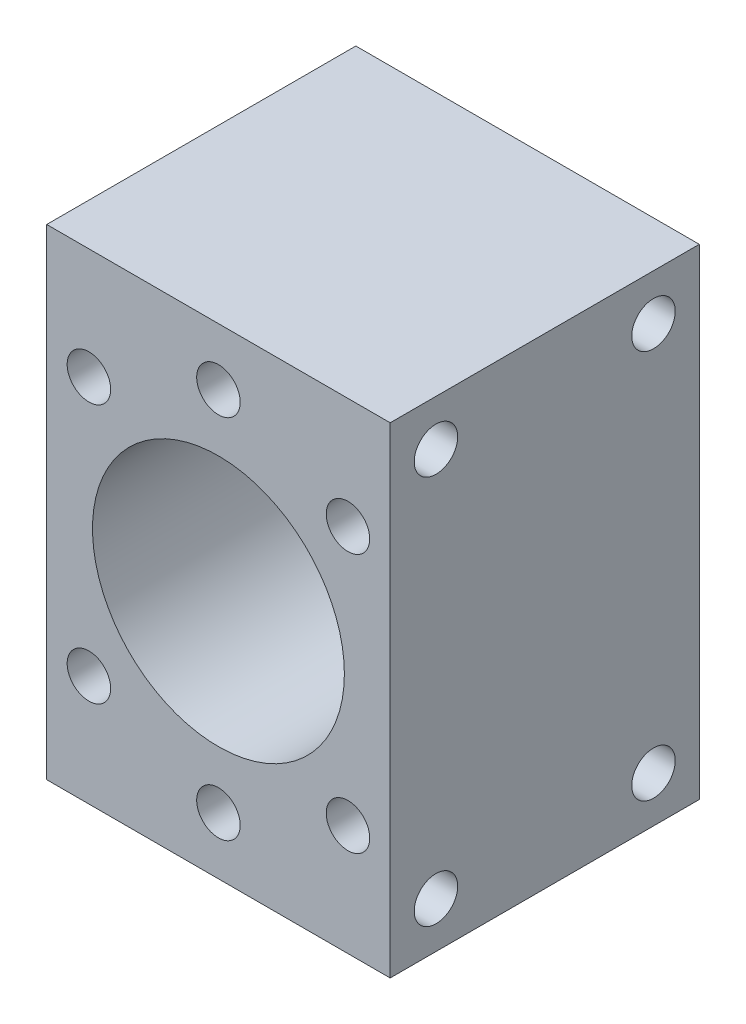
SolidWorks part; units mm, degrees
ref_plane "Front Plane" through (0, 0, 0) normal (0, 0, 1) x (1, 0, 0)
ref_plane "Top Plane" through (0, 0, 0) normal (0, 1, 0) x (1, 0, 0)
ref_plane "Right Plane" through (0, 0, 0) normal (1, 0, 0) x (0, 0, -1)
sketch "Sketch1" plane through (0, 0, 0) normal (0, 0, 1) x (1, 0, 0)
  line L3 (-15, -21) -> (15, -21)
  line L4 (-15, -21) -> (-15, 21)
  line L5 (-15, 21) -> (15, 21)
  line L6 (15, -21) -> (15, 21)
  line L7 (-15, -21) -> (15, 21) construction
  line L8 (-15, 21) -> (15, -21) construction
  dimension "D4" = 30
  dimension "D5" = 42
extrude "Boss-Extrude1" add sketch "Sketch1" along normal mid plane 27
sketch "Sketch2" plane through (0, 0, 13.5) normal (0, 0, 1) x (1, 0, 0)
  circle A0 centre (0, 0) radius 11
  dimension "D1" = 22
extrude "Cut-Extrude1" cut sketch "Sketch2" against normal through all
sketch "Sketch3" plane through (0, 0, 13.5) normal (0, 0, 1) x (1, 0, 0)
  line L0 (0, 21) -> (0, -21) construction
  line L1 (0, 0) -> (-19.8057, 19.8057) construction
  line L2 (0, 0) -> (19.0248, 19.0248) construction
  circle A2 centre (0, 0) radius 16 construction
  circle A3 centre (-11.3137, 11.3137) radius 1.9
  circle A4 centre (0, 16) radius 1.9
  circle A5 centre (11.3137, 11.3137) radius 1.9
  circle A6 centre (11.3137, -11.3137) radius 1.9
  circle A7 centre (0, -16) radius 1.9
  circle A8 centre (-11.3137, -11.3137) radius 1.9
  dimension "D3" = 32
  dimension "D4" = 3.8
  dimension "D5" = 3.8
  dimension "D6" = 3.8
  dimension "D7" = 3.8
  dimension "D8" = 3.8
  dimension "D9" = 3.8
  dimension "D1" = 45
  dimension "D2" = 45
extrude "Cut-Extrude2" cut sketch "Sketch3" against normal blind 10
sketch "Sketch6" plane through (15, 0, 0) normal (1, 0, 0) x (0, 0, -1)
  line L1 (-9.5, -17) -> (9.5, -17) construction
  line L2 (-9.5, -17) -> (-9.5, 17) construction
  line L3 (-9.5, 17) -> (9.5, 17) construction
  line L4 (9.5, -17) -> (9.5, 17) construction
  line L5 (-9.5, -17) -> (9.5, 17) construction
  line L6 (-9.5, 17) -> (9.5, -17) construction
  circle A0 centre (9.5, 17) radius 1.9
  circle A1 centre (-9.5, 17) radius 1.9
  circle A2 centre (9.5, -17) radius 1.9
  circle A3 centre (-9.5, -17) radius 1.9
  point P12 (0, 0)
  dimension "D1" = 3.8
  dimension "D2" = 3.8
  dimension "D3" = 3.8
  dimension "D4" = 3.8
  dimension "D5" = 34
  dimension "D6" = 19
extrude "Cut-Extrude3" cut sketch "Sketch6" against normal blind 10
